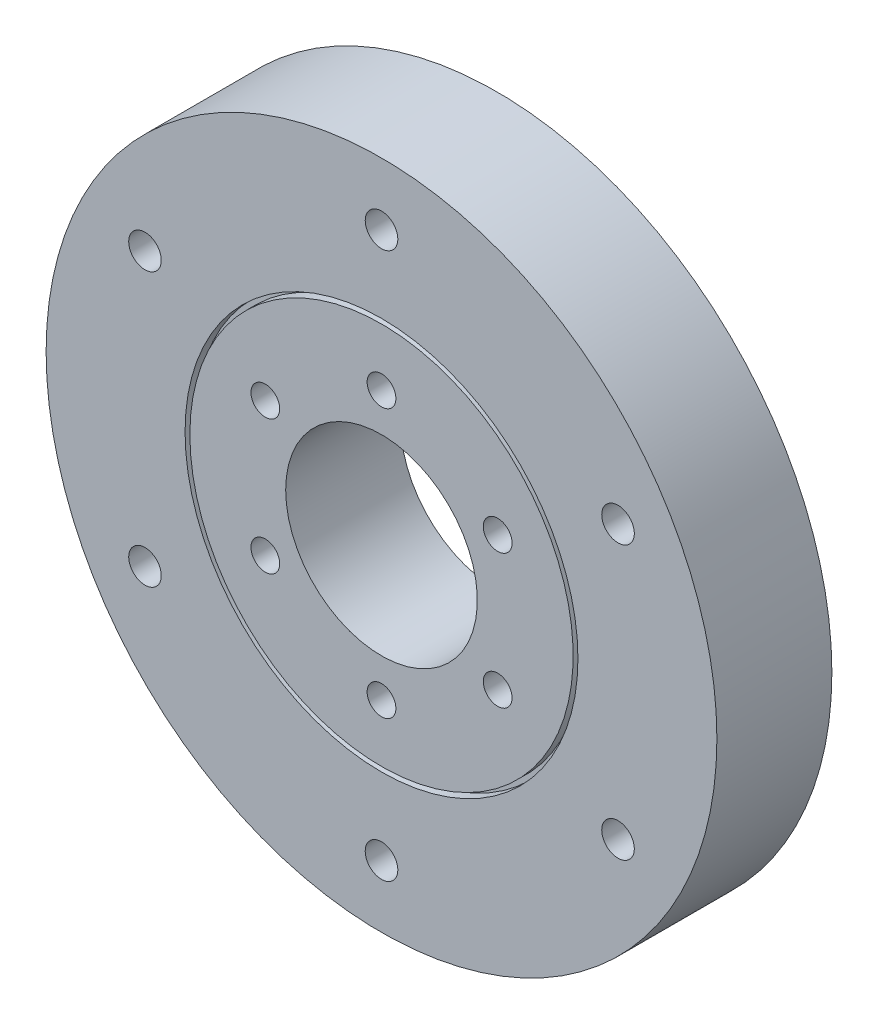
SolidWorks part; units mm, degrees
ref_plane "前视基准面" through (0, 0, 0) normal (0, 0, 1) x (1, 0, 0)
ref_plane "上视基准面" through (0, 0, 0) normal (0, 1, 0) x (1, 0, 0)
ref_plane "右视基准面" through (0, 0, 0) normal (1, 0, 0) x (0, 0, -1)
ref_axis "x轴" through (88.99, 0, 0) along (-1, 0, 0)
ref_axis "y轴" through (0, 0, -88.99) along (0, 0, 1)
ref_axis "z轴" through (0, -44, 0) along (0, 1, 0)
sketch "草图1" plane through (0, 0, 0) normal (0, 1, 0) x (1, 0, 0)
  line L0 (0, 0) -> (35, 0) construction
  line L1 (35, 0) -> (35, 6) construction
  line L2 (35, 6) -> (10, 6) construction
  line L3 (10, 6) -> (10, 0) construction
  line L4 (10, 6) -> (20, 6)
  line L5 (20, 6) -> (20, 5)
  line L6 (20, 5) -> (20.5, 5)
  line L7 (20.5, 5) -> (20.5, 6)
  line L8 (20.5, 6) -> (35, 6)
  line L9 (35, 6) -> (35, -6)
  line L10 (10, 6) -> (10, -6)
  line L11 (20.5, -5) -> (20.5, -6)
  line L12 (20.5, -6) -> (35, -6)
  line L13 (20, -5) -> (20.5, -5)
  line L14 (20, -6) -> (20, -5)
  line L15 (10, -6) -> (20, -6)
  line L16 (0, 11.2235) -> (0, -14.9391) construction
revolve "旋转1" add sketch "草图1" angle 360 about L16
sketch "草图2" plane through (0, 0, -6) normal (0, 0, -1) x (-1, 0, 0)
  circle A0 centre (0, 0) radius 14 construction
  circle A1 centre (0, 0) radius 28.5 construction
  circle A2 centre (0, 28.5) radius 1.7
  circle A10 centre (24.6817, 14.25) radius 1.7
  circle A11 centre (24.6817, -14.25) radius 1.7
  circle A12 centre (0, -28.5) radius 1.7
  circle A13 centre (-24.6817, -14.25) radius 1.7
  circle A14 centre (-24.6817, 14.25) radius 1.7
  circle A15 centre (0, 14) radius 1.5
  circle A16 centre (12.1244, 7) radius 1.5
  circle A17 centre (12.1244, -7) radius 1.5
  circle A18 centre (0, -14) radius 1.5
  circle A19 centre (-12.1244, -7) radius 1.5
  circle A20 centre (-12.1244, 7) radius 1.5
  point P20 (0, 0)
  point P22 (0, 0)
  point P33 (0, 0)
  dimension "D1" = 6
  dimension "D2" = 6
extrude "切除-拉伸1" cut sketch "草图2" against normal up to next
